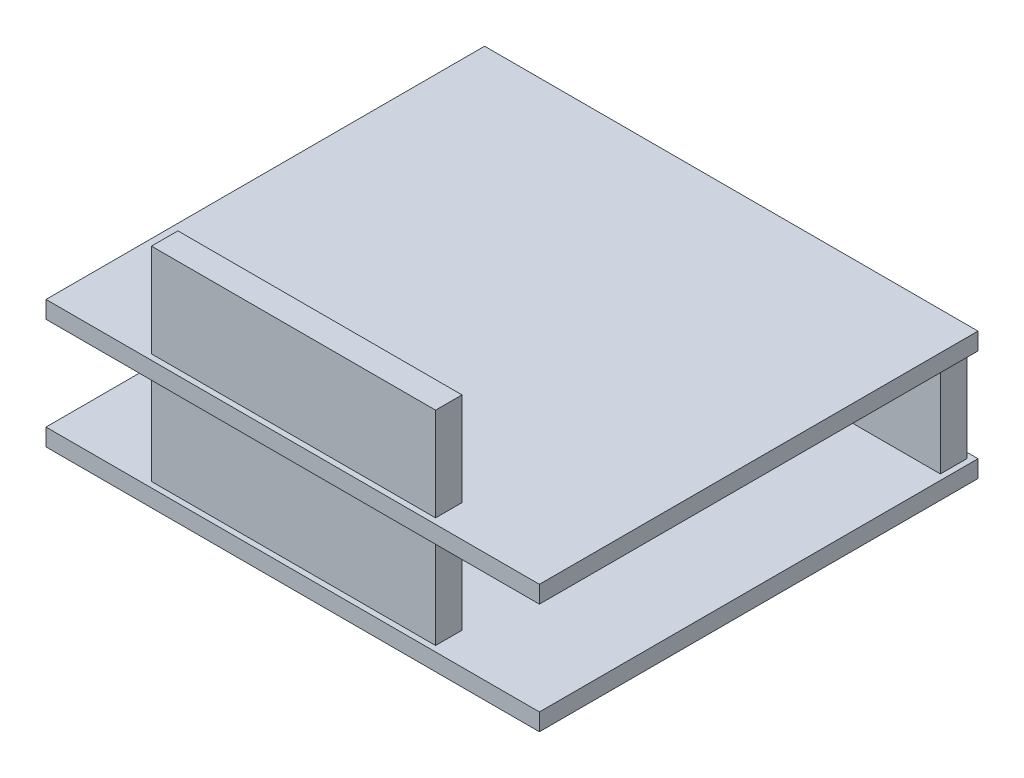
SolidWorks part; units mm, degrees
ref_plane "Front Plane" through (0, 0, 0) normal (0, 0, 1) x (1, 0, 0)
ref_plane "Top Plane" through (0, 0, 0) normal (0, 1, 0) x (1, 0, 0)
ref_plane "Right Plane" through (0, 0, 0) normal (1, 0, 0) x (0, 0, -1)
sketch "Sketch1" plane through (0, 0, 0) normal (0, 1, 0) x (1, 0, 0)
  line L1 (-22.5, -20) -> (22.5, -20)
  line L2 (-22.5, -20) -> (-22.5, 20)
  line L3 (-22.5, 20) -> (22.5, 20)
  line L4 (22.5, -20) -> (22.5, 20)
  line L5 (-22.5, -20) -> (22.5, 20) construction
  line L6 (-22.5, 20) -> (22.5, -20) construction
  point P0 (0, 0)
  dimension "D1" = 45
  dimension "D2" = 40
extrude "Boss-Extrude1" add sketch "Sketch1" along normal blind 1.57
sketch "Sketch2" plane through (0, 1.57, 0) normal (0, 1, 0) x (1, 0, 0)
  line L0 (-13.9, -20) -> (-13.9, 20) construction
  line L1 (21.99, 19.49) -> (-3.92, 19.49)
  line L2 (21.99, 19.49) -> (21.99, 17.08)
  line L3 (21.99, 17.08) -> (-3.92, 17.08)
  line L4 (-3.92, 19.49) -> (-3.92, 17.08)
  line L5 (12.52, -17.08) -> (-13.39, -17.08)
  line L6 (12.52, -17.08) -> (12.52, -19.49)
  line L7 (12.52, -19.49) -> (-13.39, -19.49)
  line L8 (-13.39, -17.08) -> (-13.39, -19.49)
  line L9 (-22.5, -20) -> (22.5, -20) construction
  line L10 (22.5, 20) -> (-22.5, 20) construction
  line L11 (22.5, -20) -> (22.5, 20) construction
  circle A0 centre (17.5, -15) radius 3.2 construction
  dimension "D6" = 6.4
  dimension "D1" = 2.41
  dimension "D2" = 2.41
  dimension "D3" = 25.91
  dimension "D4" = 25.91
  dimension "D5" = 36.4
  dimension "D7" = 5
  dimension "D8" = 5
  dimension "D9" = 0.51
  dimension "D10" = 0.51
  dimension "D11" = 0.51
  dimension "D12" = 0.51
extrude "Boss-Extrude2" add sketch "Sketch2" along normal blind 8.51
sketch "Sketch3" plane through (0, 10.08, 0) normal (0, 1, 0) x (1, 0, 0)
  line L0 (22.5, 20) -> (-22.5, 20) construction
  line L1 (22.5, -20) -> (-22.5, -20)
  line L2 (22.5, -20) -> (22.5, 20)
  line L3 (22.5, 20) -> (-22.5, 20)
  line L4 (-22.5, -20) -> (-22.5, 20)
  dimension "D1" = 45
extrude "Boss-Extrude3" add sketch "Sketch3" along normal blind 1.57
sketch "Sketch4" plane through (0, 11.65, 0) normal (0, 1, 0) x (1, 0, 0)
  line L0 (12.52, -17.08) -> (-13.39, -17.08)
  line L1 (12.52, -17.08) -> (12.52, -19.49)
  line L2 (12.52, -19.49) -> (-13.39, -19.49)
  line L3 (-13.39, -17.08) -> (-13.39, -19.49)
  line L4 (-22.5, -20) -> (22.5, -20) construction
  line L5 (22.5, -20) -> (22.5, 20) construction
  dimension "D1" = 0.51
  dimension "D2" = 2.41
  dimension "D3" = 25.91
  dimension "D4" = 9.98
extrude "Boss-Extrude4" add sketch "Sketch4" along normal blind 8.51
